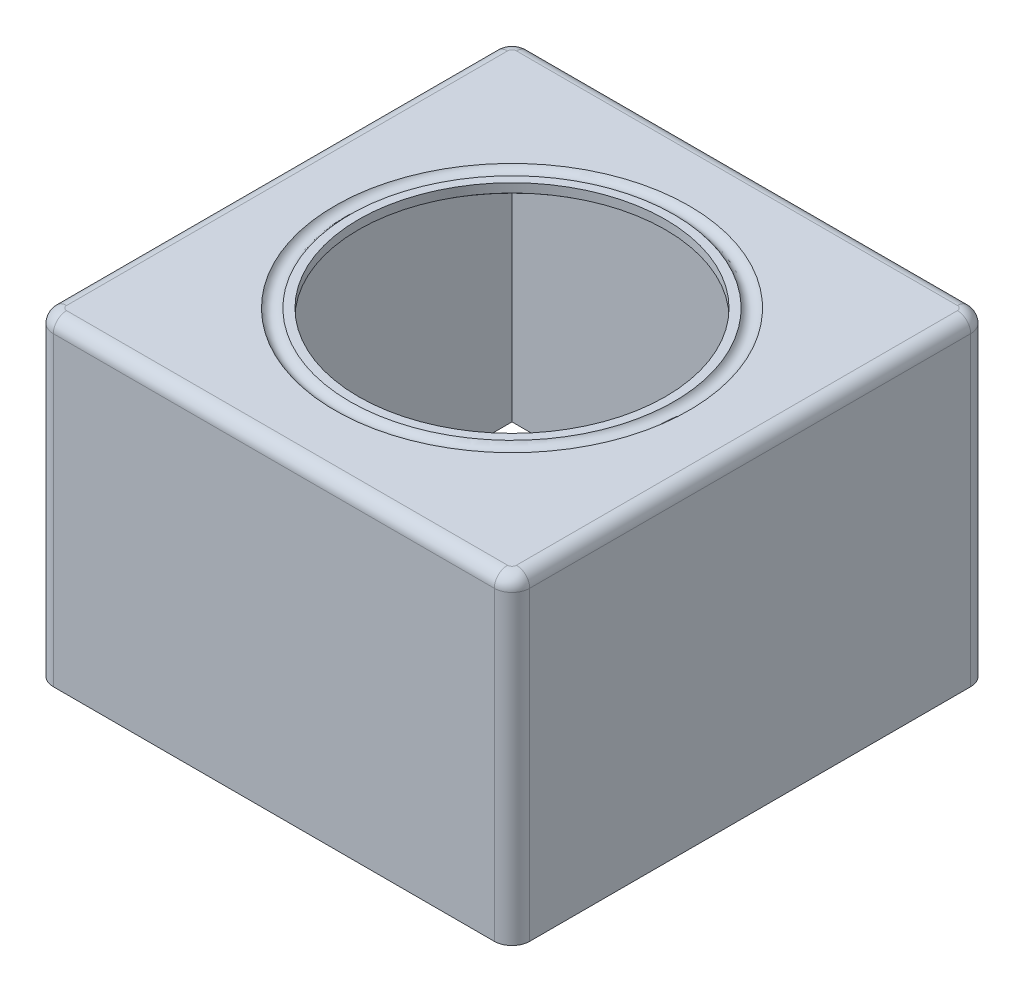
SolidWorks part; units mm, degrees
ref_plane "Front Plane" through (0, 0, 0) normal (0, 0, 1) x (1, 0, 0)
ref_plane "Top Plane" through (0, 0, 0) normal (0, 1, 0) x (1, 0, 0)
ref_plane "Right Plane" through (0, 0, 0) normal (1, 0, 0) x (0, 0, -1)
sketch "Sketch1" plane through (0, 0, 0) normal (0, 1, 0) x (1, 0, 0)
  line L1 (-49.7519, -53.7519) -> (49.7519, -53.7519)
  line L2 (-53.7519, -49.7519) -> (-53.7519, 49.7519)
  line L3 (-49.7519, 53.7519) -> (49.7519, 53.7519)
  line L4 (53.7519, -49.7519) -> (53.7519, 49.7519)
  line L5 (-53.7519, -53.7519) -> (53.7519, 53.7519) construction
  line L6 (-53.7519, 53.7519) -> (53.7519, -53.7519) construction
  line L11 (-49.7519, -49.7519) -> (49.7519, -49.7519)
  line L12 (-49.7519, -49.7519) -> (-49.7519, 49.7519)
  line L13 (-49.7519, 49.7519) -> (49.7519, 49.7519)
  line L14 (49.7519, -49.7519) -> (49.7519, 49.7519)
  line L15 (-49.7519, -49.7519) -> (49.7519, 49.7519) construction
  line L16 (-49.7519, 49.7519) -> (49.7519, -49.7519) construction
  arc A0 (-49.7519, -53.7519) -> (-53.7519, -49.7519) centre (-49.7519, -49.7519) cw
  arc A1 (49.7519, -53.7519) -> (53.7519, -49.7519) centre (49.7519, -49.7519) ccw
  arc A2 (49.7519, 53.7519) -> (53.7519, 49.7519) centre (49.7519, 49.7519) cw
  arc A3 (-53.7519, 49.7519) -> (-49.7519, 53.7519) centre (-49.7519, 49.7519) cw
  point P0 (0, 0)
  point P18 (0, 0)
  dimension "D1" = 4
extrude "Boss-Extrude1" add sketch "Sketch1" along normal blind 70
sketch "Sketch2" plane through (0, 70, 0) normal (0, 1, 0) x (1, 0, 0)
  line L0 (49.7519, 53.7519) -> (-49.7519, 53.7519) construction
  line L1 (53.7519, -53.7519) -> (-53.7519, -53.7519)
  line L2 (53.7519, -53.7519) -> (53.7519, 53.7519)
  line L3 (53.7519, 53.7519) -> (-53.7519, 53.7519)
  line L4 (-53.7519, -53.7519) -> (-53.7519, 53.7519)
  line L5 (53.7519, -53.7519) -> (-53.7519, 53.7519) construction
  line L6 (53.7519, 53.7519) -> (-53.7519, -53.7519) construction
  line L7 (-53.7519, 49.7519) -> (-53.7519, -49.7519) construction
  circle A2 centre (0, 0) radius 41.0551
  point P0 (0, 0)
  arc M3 (-53.7519, -49.7519) -> (-49.7519, -53.7519) centre (-49.7519, -49.7519) ccw
  line M4 (-49.7519, -53.7519) -> (49.7519, -53.7519)
  arc M5 (49.7519, -53.7519) -> (53.7519, -49.7519) centre (49.7519, -49.7519) ccw
  line M6 (53.7519, -49.7519) -> (53.7519, 49.7519)
  arc M7 (53.7519, 49.7519) -> (49.7519, 53.7519) centre (49.7519, 49.7519) ccw
  line M8 (49.7519, 53.7519) -> (-49.7519, 53.7519)
  arc M9 (-49.7519, 53.7519) -> (-53.7519, 49.7519) centre (-49.7519, 49.7519) ccw
  line M10 (-53.7519, 49.7519) -> (-53.7519, -49.7519)
  line M11 (-49.7519, -49.7519) -> (-49.7519, 49.7519)
  line M12 (-49.7519, 49.7519) -> (49.7519, 49.7519)
  line M13 (49.7519, 49.7519) -> (49.7519, -49.7519)
  line M14 (49.7519, -49.7519) -> (-49.7519, -49.7519)
extrude "Boss-Extrude2" add sketch "Sketch2" along normal blind 2 contours M10 M3 M4 M5 M6 M7 M8 M9 M14 M11 M12 M13 | A2 M11 M14 M13 M12 region at (0, 70, 52.2316) region at (-48.3447, 70, 0)
fillet "Fillet1" radius 3 8 edges at (52.5804, 72, 52.5804) (0, 72, 53.7519) (-52.5804, 72, 52.5804) (-53.7519, 72, 0) (-52.5804, 72, -52.5804) (0, 72, -53.7519) (52.5804, 72, -52.5804) (53.7519, 72, 0)
sketch "Sketch6" plane through (0, 0, 0) normal (1, 0, 0) x (0, 0, -1)
  line L0 (0, 0) -> (0, 101.2954) construction
  line L1 (-41.9063, 70) -> (0, 70) construction
  line L2 (49.7519, 70) -> (-49.7519, 70) construction
  line L3 (41.0551, 72) -> (-41.0551, 72) construction
  line L4 (-41.9063, 70) -> (-41.9063, 72)
  line L5 (49.7519, 72) -> (-49.7519, 72) construction
  line L6 (-39.9779, 72) -> (-41.9063, 72)
  line L7 (-36.5598, 72) -> (-34.6314, 72)
  line L8 (-34.6314, 72) -> (-34.6314, 70)
  arc A0 (-39.9779, 72) -> (-36.5598, 72) centre (-38.2688, 72.9882) ccw
  arc A1 (-41.9063, 70) -> (-34.6314, 70) centre (-38.2688, 74.2066) ccw
revolve "Revolve1" add sketch "Sketch6" angle 360 about L0
